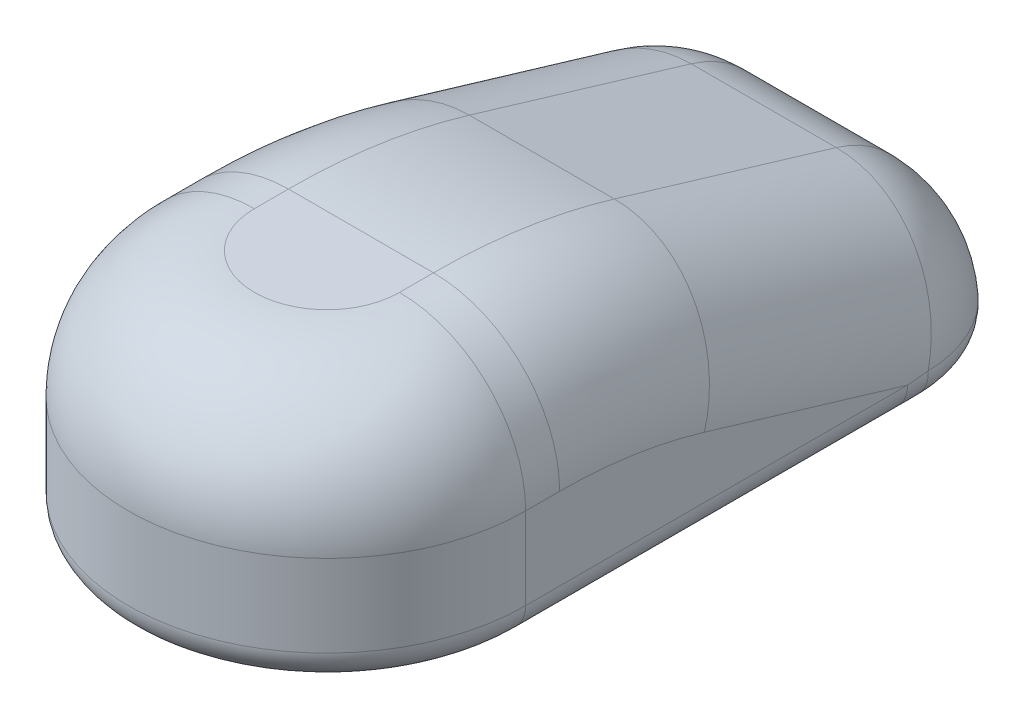
SolidWorks part; units mm, degrees
ref_plane "Front Plane" through (0, 0, 0) normal (0, 0, 1) x (1, 0, 0)
ref_plane "Top Plane" through (0, 0, 0) normal (0, 1, 0) x (1, 0, 0)
ref_plane "Right Plane" through (0, 0, 0) normal (1, 0, 0) x (0, 0, -1)
sketch "Sketch1" plane through (0, 0, 0) normal (0, 1, 0) x (1, 0, 0)
  line L0 (0, 41.75) -> (0, -73.25) construction
  line L2 (-31.5, -41.75) -> (-31.5, 21.75)
  line L3 (-11.5, 41.75) -> (11.5, 41.75)
  line L4 (31.5, -41.75) -> (31.5, 21.75)
  line L5 (-31.5, -41.75) -> (31.5, 41.75) construction
  line L6 (-31.5, 41.75) -> (31.5, -41.75) construction
  arc A0 (-31.5, -41.75) -> (31.5, -41.75) centre (0, -41.75) ccw
  arc A1 (-31.5, 21.75) -> (-11.5, 41.75) centre (-11.5, 21.75) cw
  arc A2 (11.5, 41.75) -> (31.5, 21.75) centre (11.5, 21.75) cw
  point P0 (0, 0)
  dimension "D1" = 20
  dimension "D2" = 63
  dimension "D3" = 115
extrude "Boss-Extrude1" add sketch "Sketch1" along normal blind 38
sketch "Sketch2" plane through (0, 0, 0) normal (1, 0, 0) x (0, 0, -1)
  line L0 (41.75, 19) -> (-21.7145, 38)
  line L1 (41.75, 38) -> (41.75, 0) construction
  line L2 (-41.75, 38) -> (21.75, 38) construction
  line L3 (-21.7145, 38) -> (41.75, 38)
  line L4 (41.75, 38) -> (41.75, 19)
extrude "Cut-Extrude1" cut sketch "Sketch2" against normal through all both and the other way through all
fillet "Fillet1" radius 100 1 edges at (0, 38, 21.7145)
fillet "Fillet2" radius 20 10 edges at (-31.5, 38, 39.0562) (-31.5, 36.9442, 21.8692) (-31.5, 29.3933, -7.034) (-25.6421, 20.7537, -35.8921) (0, 19, -41.75) (25.6421, 20.7537, -35.8921) (31.5, 29.3933, -7.034) (31.5, 36.9442, 21.8692) (31.5, 38, 39.0562) (0, 38, 73.25)
fillet "Fillet3" radius 5 6 edges at (31.5, 0, 10) (25.6421, 0, -35.8921) (0, 0, -41.75) (-25.6421, 0, -35.8921) (-31.5, 0, 10) (0, 0, 73.25)
